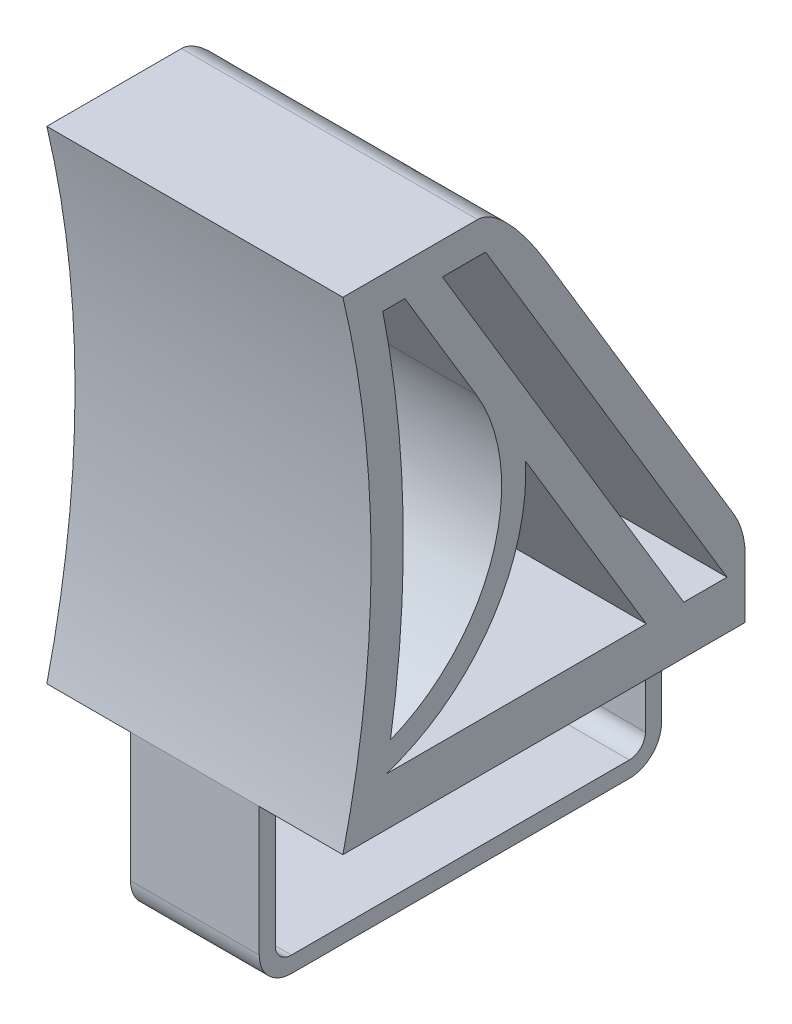
SolidWorks part; units mm, degrees
ref_plane "Front Plane" through (0, 0, 0) normal (0, 0, 1) x (1, 0, 0)
ref_plane "Top Plane" through (0, 0, 0) normal (0, 1, 0) x (1, 0, 0)
ref_plane "Right Plane" through (0, 0, 0) normal (1, 0, 0) x (0, 0, -1)
sketch "Sketch1" plane through (0, 0, 0) normal (1, 0, 0) x (0, 0, -1)
  line L0 (0, 0) -> (25, 0)
  line L4 (10, 30) -> (0, 30)
  line L5 (25, 0) -> (25, 5)
  line L6 (25, 5) -> (10, 30)
  line L7 (8.8676, 28) -> (23.8676, 3)
  line L9 (21.1854, 3) -> (6.1854, 28)
  line L11 (8.8676, 28) -> (6.1854, 28)
  line L12 (21.1854, 3) -> (23.8676, 3)
  line L13 (3.853, 28) -> (18.853, 3)
  line L14 (18.853, 3) -> (2.6711, 3)
  line L15 (3.853, 28) -> (2.4812, 28)
  arc A0 (0, 30) -> (0, 0) centre (-63.2456, 15) cw
  arc A2 (2.4812, 28) -> (2.6711, 3) centre (-63.2456, 15) cw
  arc A3 (8.2952, 20.5963) -> (2.9576, 4.6973) centre (-1.1579, 14.9244) cw
  arc A4 (11.353, 15.5) -> (2.6711, 3) centre (-1.1579, 14.9244) cw
  point P26 (11.353, 15.5)
  dimension "D4" = 5
  dimension "D5" = 65
  dimension "D10" = 2
  dimension "D11" = 2
  dimension "D12" = 1.5
  dimension "D1" = 25
  dimension "D2" = 30
  dimension "D3" = 10
  dimension "D6" = 2.3
  dimension "D7" = 2
  dimension "D8" = 3
  dimension "D9" = 2
extrude "Boss-Extrude1" add sketch "Sketch1" along normal blind 18.4 contours L4 A0 L0 L5 L6 A2 L15 L13 L14 L12 L9 L11 L7 | A4 L13 A3 A2 region at (0, 15, -2.145) region at (0, 17.9472, -9.6558)
fillet "Fillet1" radius 7 1 edges at (9.2, 30, -10) second distance 5 first distance on face at (9.2, 17.5, -17.5)
fillet "Fillet2" radius 5 1 edges at (9.2, 5, -25)
sketch "Sketch2" plane through (0, 0, 0) normal (0, -1, 0) x (-1, 0, 0)
  line L6 (-18.4, 0) -> (0, 0) construction
  line L7 (-3.2, 0) -> (-15.2, 0)
  line L8 (-3.2, 0) -> (-3.2, 25)
  line L9 (-3.2, 25) -> (-15.2, 25)
  line L10 (-15.2, 0) -> (-15.2, 25)
  line L11 (-18.4, 25) -> (0, 25) construction
  point P8 (-9.2, 25)
  point P9 (-9.2, 25)
  dimension "D1" = 12
extrude "Boss-Extrude2" add sketch "Sketch2" along normal blind 10
sketch "Sketch3" plane through (15.2, 0, 0) normal (1, 0, 0) x (0, 0, -1)
  line L0 (25, -10) -> (0, -10) construction
  line L1 (5, -6) -> (20, -6) construction
  circle A0 centre (5, -6) radius 2.2
  circle A1 centre (20, -6) radius 2.2
  point P4 (12.5, -10)
  point P7 (12.5, -6)
  dimension "D1" = 15
  dimension "D2" = 4
  dimension "D3" = 4.4
extrude "Cut-Extrude1" cut sketch "Sketch3" against normal through all
fillet "Fillet3" radius 2 2 edges at (9.2, -10, 0) (9.2, -10, -25)
ref_plane "Plane1" through (9.2, 0, 0) normal (1, 0, 0) x (0, 0, -1)
sketch "Sketch4" plane through (15.2, 0, 0) normal (1, 0, 0) x (0, 0, -1)
  line L8 (1, -1) -> (1, -8)
  line L9 (2, -9) -> (23, -9)
  line L10 (24, -8) -> (24, -1)
  line L11 (24, -1) -> (1, -1)
  line L12 (1, -1) -> (1, -8)
  line L13 (2, -9) -> (23, -9)
  line L14 (24, -8) -> (24, -1)
  line L15 (24, -1) -> (1, -1)
  arc A4 (1, -8) -> (2, -9) centre (2, -8) ccw
  arc A5 (1, -8) -> (2, -9) centre (2, -8) ccw
  arc A8 (23, -9) -> (24, -8) centre (23, -8) ccw
  arc A9 (23, -9) -> (24, -8) centre (23, -8) ccw
  circle M7 centre (5, -6) radius 2.2
  circle M8 centre (20, -6) radius 2.2
  line M9 (0, 0) -> (0, -8)
  arc M10 (0, -8) -> (2, -10) centre (2, -8) ccw
  line M11 (2, -10) -> (23, -10)
  arc M12 (23, -10) -> (25, -8) centre (23, -8) ccw
  line M13 (25, -8) -> (25, 0)
  line M14 (25, 0) -> (0, 0)
  dimension "D1" = 1
extrude "Cut-Extrude2" cut sketch "Sketch4" against normal blind 2 contours A9 L13 A5 L12 L15 L14 M14 M9 M10 M11 M12 M13 | L13 A9 L14 L15 L12 A5 M7 M8 region at (15.2, -4.7909, -12.5) region at (15.2, -0.2693, -12.5)
extrude "Cut-Extrude3" cut sketch "Sketch4<3>" against normal up to surface (6 mm away) up to plane "Plane1"
sketch "Sketch4<3>" plane through (15.2, 0, 0) normal (1, 0, 0) x (0, 0, -1) same geometry as "Sketch4"
mirror "Mirror1" about plane through (9.2, 0, 0) normal (1, 0, 0) of "Cut-Extrude3", "Cut-Extrude2"
